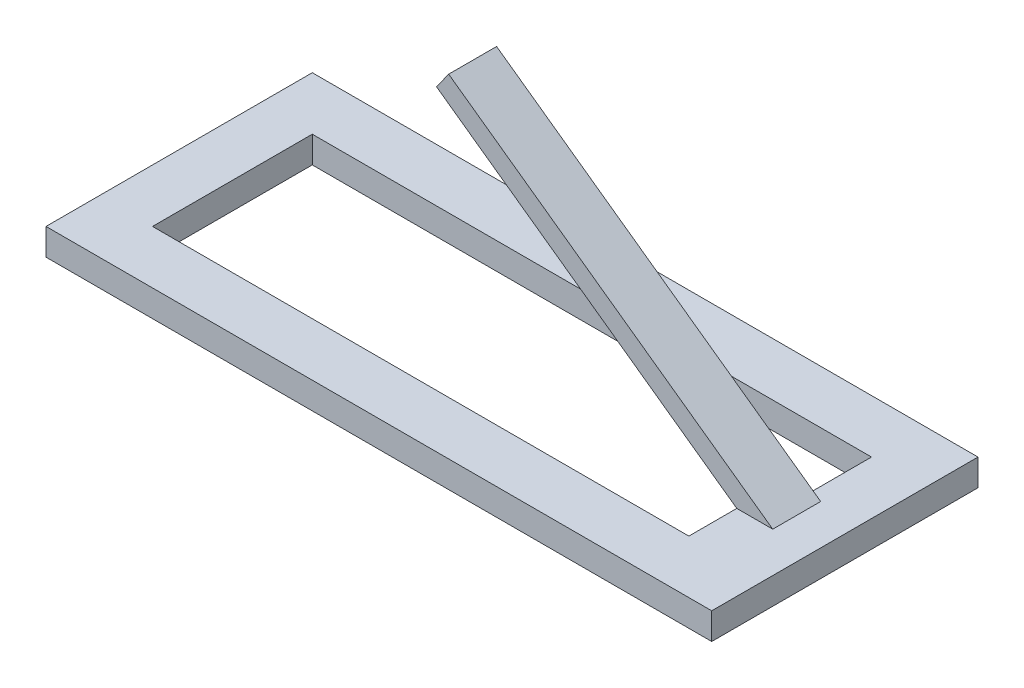
SolidWorks part; units mm, degrees
ref_plane "Front Plane" through (0, 0, 0) normal (0, 0, 1) x (1, 0, 0)
ref_plane "Top Plane" through (0, 0, 0) normal (0, 1, 0) x (1, 0, 0)
ref_plane "Right Plane" through (0, 0, 0) normal (1, 0, 0) x (0, 0, -1)
sketch "Sketch1" plane through (0, 0, 0) normal (0, 1, 0) x (1, 0, 0)
  line L0 (-63.7778, 60) -> (146.2222, 60)
  line L1 (-83.7778, 80) -> (166.2222, 80)
  line L2 (-83.7778, 80) -> (-83.7778, 60)
  line L4 (166.2222, 80) -> (166.2222, 60)
  line L6 (-83.7778, 0) -> (-83.7778, -20)
  line L7 (-83.7778, -20) -> (166.2222, -20)
  line L8 (166.2222, 0) -> (166.2222, -20)
  line L9 (-83.7778, 60) -> (-63.7778, 60)
  line L10 (-83.7778, 60) -> (-83.7778, 0)
  line L11 (-83.7778, 0) -> (-63.7778, 0)
  line L12 (-63.7778, 60) -> (-63.7778, 0)
  line L13 (166.2222, 60) -> (146.2222, 60)
  line L14 (166.2222, 60) -> (166.2222, 0)
  line L15 (166.2222, 0) -> (146.2222, 0)
  line L16 (146.2222, 60) -> (146.2222, 0)
  line L17 (146.2222, 0) -> (-63.7778, 0)
  dimension "D1" = 20
  dimension "D2" = 20
  dimension "D3" = 20
  dimension "D4" = 250
  dimension "D5" = 250
  dimension "D6" = 20
extrude "Boss-Extrude2" add sketch "Sketch1" along normal blind 10 contours L13 L4 L1 L2 L9 L0 | L13 L16 L15 L14 | L15 L17 L11 L6 L7 L8 | L12 L9 L10 L11 region at (41.2222, 0, -70) region at (-73.7778, 0, -30) region at (156.2222, 0, -30) region at (41.2222, 0, 10)
sketch "Sketch2" plane through (0, 0, 0) normal (0, 0, 1) x (1, 0, 0)
  line L0 (161.9405, 2.2662) -> (29.4465, 97.1387)
  line L1 (29.4465, 97.1387) -> (24.8697, 90.7469)
  line L2 (24.8697, 90.7469) -> (148.4373, 2.2662)
  line L3 (148.4373, 2.2662) -> (161.9405, 2.2662)
extrude "Boss-Extrude3" add sketch "Sketch2" against normal blind 36
sketch "Sketch3" plane through (0, 0, 0) normal (0, 0, 1) x (1, 0, 0)
  line L2 (152.1947, 10) -> (12.1947, 10)
  line L3 (152.1947, 10) -> (152.1947, 150)
  line L4 (152.1947, 150) -> (12.1947, 150)
  line L5 (12.1947, 10) -> (12.1947, 150)
  dimension "D1" = 140
  dimension "D2" = 140
extrude "Cut-Extrude1" cut sketch "Sketch3" against normal blind 18
